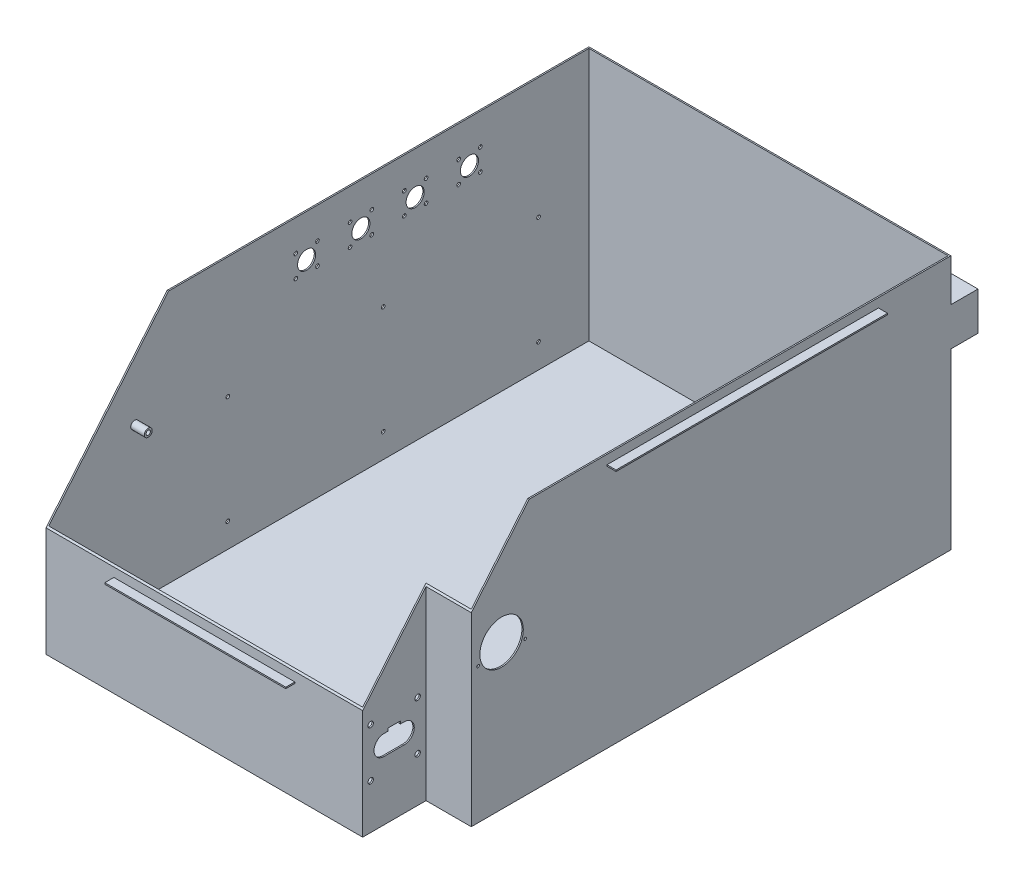
SolidWorks part; units mm, degrees
ref_plane "Front Plane" through (0, 0, 0) normal (0, 0, 1) x (1, 0, 0)
ref_plane "Top Plane" through (0, 0, 0) normal (0, 1, 0) x (1, 0, 0)
ref_plane "Right Plane" through (0, 0, 0) normal (1, 0, 0) x (0, 0, -1)
sketch "Sketch1" plane through (0, 0, 0) normal (0, 1, 0) x (1, 0, 0)
  line L1 (-200, 237.8263) -> (200, 237.8263)
  line L2 (-200, 237.8263) -> (-200, -362.1737)
  line L3 (-200, -362.1737) -> (150, -362.1737)
  line L4 (200, 237.8263) -> (200, -292.1737)
  line L6 (200, -292.1737) -> (150, -292.1737)
  line L7 (150, -292.1737) -> (150, -362.1737)
  line L8 (0, -55) -> (0, 55) construction
  point P1 (0, 237.8263)
  dimension "D1" = 600
  dimension "D2" = 400
  dimension "D5" = 70
  dimension "D6" = 50
extrude "Boss-Extrude1" add sketch "Sketch1" along normal blind 1.5
sketch "Sketch2" plane through (0, 1.5, 0) normal (0, 1, 0) x (1, 0, 0)
  line L60 (-198.5, 236.3263) -> (-198.5, -360.6737)
  line L61 (-198.5, -360.6737) -> (148.5, -360.6737)
  line L62 (148.5, -360.6737) -> (148.5, -290.6737)
  line L63 (148.5, -290.6737) -> (198.5, -290.6737)
  line L64 (198.5, -290.6737) -> (198.5, 236.3263)
  line L65 (198.5, 236.3263) -> (-198.5, 236.3263)
  line L66 (-200, 237.8263) -> (-200, -362.1737)
  line L67 (-200, -362.1737) -> (150, -362.1737)
  line L68 (150, -362.1737) -> (150, -292.1737)
  line L69 (150, -292.1737) -> (200, -292.1737)
  line L70 (200, -292.1737) -> (200, 237.8263)
  line L71 (200, 237.8263) -> (-200, 237.8263)
  line L72 (-200, 237.8263) -> (-200, -362.1737)
  line L73 (-200, -362.1737) -> (150, -362.1737)
  line L74 (150, -362.1737) -> (150, -292.1737)
  line L75 (150, -292.1737) -> (200, -292.1737)
  line L76 (200, -292.1737) -> (200, 237.8263)
  line L77 (200, 237.8263) -> (-200, 237.8263)
  dimension "D1" = 0
  dimension "D2" = 1.5
extrude "Boss-Extrude2" add sketch "Sketch2" along normal blind 280
sketch "Sketch3" plane through (-200, 0, 0) normal (-1, 0, 0) x (0, 0, 1)
  line L3 (362.1737, 281.5) -> (362.1737, 0) construction
  line L4 (362.1737, 121.1176) -> (228.1952, 281.5)
  line L6 (-237.8263, 281.5) -> (362.1737, 281.5) construction
  line L9 (362.1737, 281.5) -> (362.1737, 121.1176)
  line L10 (228.1952, 281.5) -> (362.1737, 281.5)
sketch "Sketch4" plane through (0, 0, -237.8263) normal (0, 0, -1) x (-1, 0, 0)
  line L0 (-200, 281.5) -> (-200, 0) construction
  line L1 (-200, 234.6761) -> (200, 234.6761)
  line L2 (-200, 234.6761) -> (-200, 192.2905)
  line L3 (-200, 192.2905) -> (200, 192.2905)
  line L4 (200, 234.6761) -> (200, 192.2905)
  line L5 (200, 281.5) -> (200, 0) construction
extrude "Boss-Extrude3" add sketch "Sketch4" along normal blind 30
extrude "Cut-Extrude1" cut sketch "Sketch3" against normal through all both and the other way through all
sketch "Sketch5" plane through (-200, 0, 0) normal (-1, 0, 0) x (0, 0, 1)
  line L0 (-116.3263, 223.1259) -> (-116.3263, 247.1259) construction
  line L5 (-116.3263, 223.1259) -> (-92.3263, 223.1259) construction
  line L6 (-116.3263, 247.1259) -> (-92.3263, 247.1259) construction
  line L7 (-92.3263, 223.1259) -> (-92.3263, 247.1259) construction
  line L8 (-116.3263, 223.1259) -> (-92.3263, 247.1259) construction
  line L9 (-116.3263, 247.1259) -> (-92.3263, 223.1259) construction
  line L10 (-56.3263, 223.1259) -> (-56.3263, 247.1259) construction
  line L11 (-56.3263, 223.1259) -> (-32.3263, 223.1259) construction
  line L12 (-56.3263, 247.1259) -> (-32.3263, 247.1259) construction
  line L13 (-32.3263, 223.1259) -> (-32.3263, 247.1259) construction
  line L14 (-56.3263, 223.1259) -> (-32.3263, 247.1259) construction
  line L15 (-56.3263, 247.1259) -> (-32.3263, 223.1259) construction
  line L16 (3.6737, 223.1259) -> (3.6737, 247.1259) construction
  line L17 (3.6737, 223.1259) -> (27.6737, 223.1259) construction
  line L18 (3.6737, 247.1259) -> (27.6737, 247.1259) construction
  line L19 (27.6737, 223.1259) -> (27.6737, 247.1259) construction
  line L20 (3.6737, 223.1259) -> (27.6737, 247.1259) construction
  line L21 (3.6737, 247.1259) -> (27.6737, 223.1259) construction
  line L22 (63.6737, 223.1259) -> (63.6737, 247.1259) construction
  line L23 (63.6737, 223.1259) -> (87.6737, 223.1259) construction
  line L24 (63.6737, 247.1259) -> (87.6737, 247.1259) construction
  line L25 (87.6737, 223.1259) -> (87.6737, 247.1259) construction
  line L26 (63.6737, 223.1259) -> (87.6737, 247.1259) construction
  line L27 (63.6737, 247.1259) -> (87.6737, 223.1259) construction
  line L28 (-236.3263, 281.5) -> (-236.3263, 1.5) construction
  circle A0 centre (-116.3263, 247.1259) radius 2
  circle A1 centre (-116.3263, 223.1259) radius 2
  circle A2 centre (-92.3263, 223.1259) radius 2
  circle A3 centre (-92.3263, 247.1259) radius 2
  circle A4 centre (-104.3263, 235.1259) radius 10
  circle A5 centre (-56.3263, 247.1259) radius 2
  circle A6 centre (-56.3263, 223.1259) radius 2
  circle A7 centre (-32.3263, 223.1259) radius 2
  circle A8 centre (-32.3263, 247.1259) radius 2
  circle A9 centre (-44.3263, 235.1259) radius 10
  circle A10 centre (3.6737, 247.1259) radius 2
  circle A11 centre (3.6737, 223.1259) radius 2
  circle A12 centre (27.6737, 223.1259) radius 2
  circle A13 centre (27.6737, 247.1259) radius 2
  circle A14 centre (15.6737, 235.1259) radius 10
  circle A15 centre (63.6737, 247.1259) radius 2
  circle A16 centre (63.6737, 223.1259) radius 2
  circle A17 centre (87.6737, 223.1259) radius 2
  circle A18 centre (87.6737, 247.1259) radius 2
  circle A19 centre (75.6737, 235.1259) radius 10
  point P9 (-104.3263, 235.1259)
  point P24 (-44.3263, 235.1259)
  point P38 (15.6737, 235.1259)
  point P52 (75.6737, 235.1259)
  dimension "D2" = 20
  dimension "D5" = 4
  dimension "D1" = 24
  dimension "D3" = 24
  dimension "D4" = 24
  dimension "D7" = 120
  dimension "D6" = 4
sketch "Sketch6" plane through (-198.5, 0, 0) normal (1, 0, 0) x (0, 0, -1)
  arc A0 (151.1392, 167.4539) -> (156.7272, 167.4539) centre (153.9332, 167.4539) ccw construction
  arc A1 (-68.8756, 167.4539) -> (-63.2876, 167.4539) centre (-66.0816, 167.4539) ccw construction
  arc A2 (-178.883, 167.4539) -> (-173.295, 167.4539) centre (-176.089, 167.4539) ccw construction
  arc A3 (151.1392, 167.4539) -> (156.7272, 167.4539) centre (153.9332, 167.4539) ccw
  arc A4 (-68.8756, 167.4539) -> (-63.2876, 167.4539) centre (-66.0816, 167.4539) ccw
  arc A5 (-178.883, 167.4539) -> (-173.295, 167.4539) centre (-176.089, 167.4539) ccw
  circle A6 centre (-176.089, 167.4539) radius 2.794
  circle A7 centre (-176.089, 167.4539) radius 4.5
  circle A8 centre (-64.4633, 167.4539) radius 4.5
  circle A9 centre (-64.4633, 167.4539) radius 2.794
  circle A10 centre (155.5515, 167.4539) radius 2.794
  circle A11 centre (155.5515, 167.4539) radius 4.5
  dimension "D1" = 9
extrude "Boss-Extrude4" [suppressed] add sketch "Sketch6" along normal blind 50 contours A4 A9 | A8 | A7 | A6 | A11 | A10
sketch "Sketch8" plane through (-198.5, 0, 0) normal (1, 0, 0) x (0, 0, -1)
  line L0 (236.3263, 1.5) -> (-360.6737, 1.5) construction
  line L1 (-360.6737, 122.9132) -> (-360.6737, 1.5) construction
  circle A0 centre (-265.6737, 172.2) radius 2.39
  circle A1 centre (-265.6737, 172.2) radius 4.39
  circle A2 centre (-265.6737, 16.5) radius 2.39
  circle A3 centre (-265.6737, 16.5) radius 4.39
  dimension "D3" = 4.78
  dimension "D4" = 2
  dimension "D1" = 155.7
  dimension "D2" = 15
  dimension "D5" = 95
extrude "Boss-Extrude5" add sketch "Sketch8" along normal blind 15
sketch "Sketch10" plane through (148.5, 0, 0) normal (-1, 0, 0) x (0, 0, 1)
  line L0 (316.1737, 86.5) -> (321.4237, 86.5) construction
  line L1 (316.1737, 66.5) -> (338.6737, 66.5) construction
  line L2 (338.6737, 76.5) -> (316.1737, 76.5) construction
  line L3 (360.6737, 1.5) -> (290.6737, 1.5) construction
  line L5 (321.4237, 86.5) -> (321.4237, 89.5) construction
  line L6 (321.4237, 89.5) -> (333.4237, 89.5) construction
  line L7 (333.4237, 86.5) -> (333.4237, 89.5) construction
  line L8 (360.6737, 122.9132) -> (360.6737, 1.5) construction
  line L9 (333.4237, 86.5) -> (338.6737, 86.5) construction
  line L10 (320.4237, 90.5) -> (334.4237, 90.5)
  line L11 (334.4237, 87.5) -> (334.4237, 90.5)
  line L12 (334.4237, 87.5) -> (338.6737, 87.5)
  line L13 (316.1737, 65.5) -> (338.6737, 65.5)
  line L14 (316.1737, 87.5) -> (320.4237, 87.5)
  line L15 (320.4237, 87.5) -> (320.4237, 90.5)
  line L17 (301.4737, 49.55) -> (353.3737, 49.55) construction
  line L18 (301.4737, 49.55) -> (301.4737, 103.45) construction
  line L19 (301.4737, 103.45) -> (353.3737, 103.45) construction
  line L20 (353.3737, 49.55) -> (353.3737, 103.45) construction
  line L21 (301.4737, 49.55) -> (353.3737, 103.45) construction
  line L22 (301.4737, 103.45) -> (353.3737, 49.55) construction
  arc A0 (316.1737, 86.5) -> (316.1737, 66.5) centre (316.1737, 76.5) ccw construction
  arc A1 (338.6737, 66.5) -> (338.6737, 86.5) centre (338.6737, 76.5) ccw construction
  arc A2 (338.6737, 65.5) -> (338.6737, 87.5) centre (338.6737, 76.5) ccw
  arc A3 (316.1737, 87.5) -> (316.1737, 65.5) centre (316.1737, 76.5) ccw
  circle A4 centre (301.4737, 103.45) radius 3
  circle A5 centre (353.3737, 103.45) radius 3
  circle A6 centre (301.4737, 49.55) radius 3
  circle A7 centre (353.3737, 49.55) radius 3
  point P12 (327.4237, 89.5)
  point P13 (327.4237, 76.5)
  point P26 (327.4237, 76.5)
  dimension "D1" = 65
  dimension "D2" = 22.5
  dimension "D6" = 20
  dimension "D10" = 6
  dimension "D3" = 22
  dimension "D4" = 12
  dimension "D5" = 3
  dimension "D8" = 51.9
  dimension "D9" = 53.9
  dimension "D7" = 1
extrude "Cut-Extrude2" cut sketch "Sketch10" against normal up to surface (1.5 mm away) contours L0 L7 L6 L5 | L2 A1 L0 A0 | A1 L2 A0 L1 | A0 | A1 | L14 A3 L13 A2 L12 L11 L10 L15 | A4 | A5 | A7 | A6 region at (148.5, 77.0724, 327.4237) region at (148.5, 103.45, 301.4737) region at (148.5, 103.45, 353.3737) region at (148.5, 49.55, 353.3737) up to face at (150, 81.5076, 327.1737)
sketch "Sketch11" plane through (148.5, 0, 0) normal (-1, 0, 0) x (0, 0, 1)
  line L0 (298.4737, 103.43) -> (298.4737, 49.53) construction
  line L13 (316.1737, 66.5) -> (338.6737, 66.5) construction
  line L14 (316.1737, 86.5) -> (321.4237, 86.5) construction
  line L15 (316.1737, 66.5) -> (338.6737, 66.5)
  line L19 (316.1737, 86.5) -> (318.4237, 86.5)
  line L20 (334.4237, 90.5) -> (320.4237, 90.5)
  line L21 (334.4237, 90.5) -> (320.4237, 90.5)
  line L22 (334.4237, 87.5) -> (334.4237, 90.5)
  line L23 (334.4237, 87.5) -> (334.4237, 90.5)
  line L28 (330.4237, 86.5) -> (321.4237, 86.5)
  line L29 (316.2509, 66) -> (338.7144, 66)
  line L30 (330.9237, 86) -> (320.7529, 86)
  line L31 (330.9237, 86) -> (330.9237, 91)
  line L32 (330.9237, 91) -> (317.9237, 91)
  line L33 (317.9237, 91) -> (317.9237, 87)
  line L34 (316.2509, 87) -> (317.9237, 87)
  line L36 (298.4737, 103.43) -> (350.3737, 103.43) construction
  line L43 (334.4237, 90.5) -> (320.4237, 90.5)
  line L44 (334.4237, 90.5) -> (320.4237, 90.5)
  line L45 (334.4237, 87.5) -> (334.4237, 90.5)
  line L46 (334.4237, 87.5) -> (334.4237, 90.5)
  line L47 (338.6737, 87.5) -> (334.4237, 87.5)
  line L48 (338.6737, 87.5) -> (334.4237, 87.5)
  line L49 (316.1737, 65.5) -> (338.6737, 65.5)
  line L50 (316.1737, 65.5) -> (338.6737, 65.5)
  line L51 (320.4237, 87.5) -> (316.1737, 87.5)
  line L52 (320.4237, 87.5) -> (316.1737, 87.5)
  line L53 (320.4237, 90.5) -> (320.4237, 87.5)
  line L54 (320.4237, 90.5) -> (320.4237, 87.5)
  line L55 (334.4237, 90.5) -> (320.4237, 90.5)
  line L56 (334.4237, 90.5) -> (320.4237, 90.5)
  line L57 (334.4237, 87.5) -> (334.4237, 90.5)
  line L58 (334.4237, 87.5) -> (334.4237, 90.5)
  line L59 (338.6737, 87.5) -> (334.4237, 87.5)
  line L60 (338.6737, 87.5) -> (334.4237, 87.5)
  line L61 (316.1737, 65.5) -> (338.6737, 65.5)
  line L62 (316.1737, 65.5) -> (338.6737, 65.5)
  line L63 (320.4237, 87.5) -> (316.1737, 87.5)
  line L64 (320.4237, 87.5) -> (316.1737, 87.5)
  line L65 (320.4237, 90.5) -> (320.4237, 87.5)
  line L66 (320.4237, 90.5) -> (320.4237, 87.5)
  line L67 (330.4237, 86.5) -> (330.4237, 90.5) construction
  line L68 (330.4237, 90.5) -> (318.4237, 90.5) construction
  line L69 (318.4237, 90.5) -> (318.4237, 86.5) construction
  line L70 (338.6737, 87.5) -> (334.4237, 87.5)
  line L71 (338.6737, 87.5) -> (334.4237, 87.5)
  line L72 (316.1737, 65.5) -> (338.6737, 65.5)
  line L73 (316.1737, 65.5) -> (338.6737, 65.5)
  line L74 (320.4237, 87.5) -> (316.1737, 87.5)
  line L75 (320.4237, 87.5) -> (316.1737, 87.5)
  line L76 (320.4237, 90.5) -> (320.4237, 87.5)
  line L77 (320.4237, 90.5) -> (320.4237, 87.5)
  arc A4 (338.7144, 66) -> (320.7529, 86) centre (336.1498, 81.7622) ccw
  arc A5 (338.6737, 65.5) -> (338.6737, 87.5) centre (338.6737, 76.5) ccw
  arc A7 (338.6737, 65.5) -> (338.6737, 87.5) centre (338.6737, 76.5) ccw
  arc A9 (316.2509, 87) -> (316.2509, 66) centre (312.9721, 76.5) ccw
  circle A10 centre (298.4737, 103.43) radius 3
  circle A11 centre (298.4737, 49.53) radius 3
  circle A12 centre (350.3737, 103.43) radius 3
  circle A13 centre (350.3737, 49.53) radius 3
  arc A16 (338.6737, 66.5) -> (321.4237, 86.5) centre (336.1498, 81.7622) ccw construction
  arc A17 (338.6737, 65.5) -> (338.6737, 87.5) centre (338.6737, 76.5) ccw
  arc A18 (316.1737, 87.5) -> (316.1737, 65.5) centre (316.1737, 76.5) ccw
  arc A19 (316.1737, 87.5) -> (316.1737, 65.5) centre (316.1737, 76.5) ccw
  arc A20 (316.1737, 86.5) -> (316.1737, 66.5) centre (312.9721, 76.5) ccw construction
  arc A21 (338.6737, 65.5) -> (338.6737, 87.5) centre (338.6737, 76.5) ccw
  arc A22 (316.1737, 87.5) -> (316.1737, 65.5) centre (316.1737, 76.5) ccw
  arc A23 (316.1737, 87.5) -> (316.1737, 65.5) centre (316.1737, 76.5) ccw
  arc A24 (338.6737, 65.5) -> (338.6737, 87.5) centre (338.6737, 76.5) ccw
  arc A25 (338.6737, 65.5) -> (338.6737, 87.5) centre (338.6737, 76.5) ccw
  arc A26 (316.1737, 87.5) -> (316.1737, 65.5) centre (316.1737, 76.5) ccw
  arc A27 (316.1737, 87.5) -> (316.1737, 65.5) centre (316.1737, 76.5) ccw
  dimension "D5" = 6
  dimension "D6" = 51.9
  dimension "D7" = 53.9
  dimension "D1" = 0
  dimension "D2" = 0
  dimension "D3" = 0
  dimension "D4" = 0.5
extrude "Cut-Extrude3" [suppressed] cut sketch "Sketch11" against normal through all
sketch "Sketch14" plane through (148.5, 0, 0) normal (-1, 0, 0) x (0, 0, 1)
  line L0 (362.1737, 121.1176) -> (362.1737, 0) construction
  line L1 (362.1737, 0) -> (292.1737, 0) construction
  circle A0 centre (297.2737, 103.43) radius 3
  circle A1 centre (349.1737, 103.43) radius 3
  circle A2 centre (349.1737, 49.53) radius 3
  circle A3 centre (297.2737, 49.53) radius 3
  dimension "D5" = 6
  dimension "D1" = 51.9
  dimension "D2" = 53.9
  dimension "D3" = 13
  dimension "D4" = 103.43
extrude "Cut-Extrude4" [suppressed] cut sketch "Sketch14" against normal up to surface (1.5 mm away) up to face at (150, 49.55, 304.4737)
sketch "Sketch15" plane through (198.5, 0, 0) normal (-1, 0, 0) x (0, 0, 1)
  line L1 (-151.3263, 252.1363) -> (-136.3263, 252.1363)
  line L2 (-151.3263, 252.1363) -> (-151.3263, 250.6363)
  line L3 (-151.3263, 250.6363) -> (-136.3263, 250.6363)
  line L4 (-136.3263, 252.1363) -> (-136.3263, 250.6363)
  line L5 (-236.3263, 281.5) -> (-236.3263, 1.5) construction
  line L6 (126.6737, 252.1363) -> (146.6737, 252.1363)
  line L7 (126.6737, 250.6363) -> (146.6737, 250.6363)
  line L8 (126.6737, 252.1363) -> (126.6737, 250.6363)
  line L9 (146.6737, 252.1363) -> (146.6737, 250.6363)
  dimension "D1" = 1.5
  dimension "D2" = 15
  dimension "D3" = 85
  dimension "D4" = 363
  dimension "D5" = 20
extrude "Boss-Extrude6" add sketch "Sketch15" along normal blind 13
ref_plane "Plane1" through (0, 0, -131.3263) normal (0, 0, -1) x (-1, 0, 0)
sketch "Sketch17" plane through (0, 0, -136.3263) normal (0, 0, 1) x (1, 0, 0)
  line L0 (198.5, 250.6363) -> (198.5, 235.6363)
  line L1 (198.5, 281.5) -> (198.5, 206.7085) construction
  line L2 (198.5, 235.6363) -> (185.5, 250.6363)
  line L3 (185.5, 250.6363) -> (198.5, 250.6363)
  dimension "D1" = 15
extrude "Boss-Extrude7" add sketch "Sketch17" against normal blind 1.5
ref_plane "Plane2" through (0, 0, 126.6737) normal (0, 0, 1) x (1, 0, 0)
sketch "Sketch18" plane through (0, 0, 126.6737) normal (0, 0, 1) x (1, 0, 0)
  line L0 (198.5, 250.6363) -> (198.5, 235.6363)
  line L1 (198.5, 281.5) -> (198.5, 206.7085) construction
  line L2 (198.5, 235.6363) -> (185.5, 250.6363)
  line L3 (185.5, 250.6363) -> (198.5, 250.6363)
  dimension "D1" = 15
extrude "Boss-Extrude8" add sketch "Sketch18" along normal blind 1.5
sketch "Sketch20" plane through (0, 252.1363, 0) normal (0, 1, 0) x (1, 0, 0)
  line L1 (185.5, 151.3263) -> (198.5, 151.3263) construction
  line L2 (185.5, 136.3263) -> (185.5, 151.3263) construction
  line L3 (185.5, -146.6737) -> (198.5, -146.6737) construction
  line L4 (185.5, -146.6737) -> (185.5, -126.6737) construction
  circle A0 centre (193, 144.3263) radius 2.4159
  circle A1 centre (195.5, -139.6737) radius 2
  dimension "D3" = 4
  dimension "D1" = 7
  dimension "D2" = 7.5
  dimension "D4" = 7
  dimension "D5" = 10
extrude "Cut-Extrude5" cut sketch "Sketch20" against normal up to surface (1.5 mm away) up to face at (192, 250.6363, -144.5763)
extrude "Cut-Extrude7" cut sketch "Sketch5" against normal up to surface (1.5 mm away) up to face at (-198.5, 16.5, 261.2837)
sketch "Sketch21" plane through (0, 0, -237.8263) normal (0, 0, -1) x (-1, 0, 0)
  line L0 (-200, 281.5) -> (200, 281.5) construction
  line L1 (-150, 271.5) -> (150, 271.5)
  line L2 (-150, 271.5) -> (-150, 270)
  line L3 (-150, 270) -> (150, 270)
  line L4 (150, 271.5) -> (150, 270)
  point P6 (0, 281.5)
  point P7 (0, 271.5)
  dimension "D1" = 1.5
  dimension "D2" = 300
  dimension "D3" = 10
extrude "Boss-Extrude9" add sketch "Sketch21" along normal blind 10
sketch "Sketch22" plane through (-200, 0, 0) normal (-1, 0, 0) x (0, 0, 1)
  line L0 (-237.8263, 281.5) -> (228.1952, 281.5) construction
  line L1 (-157.8263, 271.5) -> (142.1737, 271.5)
  line L2 (-157.8263, 271.5) -> (-157.8263, 270)
  line L3 (-157.8263, 270) -> (142.1737, 270)
  line L4 (142.1737, 271.5) -> (142.1737, 270)
  line L5 (-237.8263, 281.5) -> (-237.8263, 234.6761) construction
  dimension "D1" = 1.5
  dimension "D2" = 10
  dimension "D3" = 80
  dimension "D4" = 300
extrude "Boss-Extrude10" add sketch "Sketch22" along normal blind 10
ref_plane "Plane3" through (0, 0, -77.8263) normal (0, 0, -1) x (-1, 0, 0)
sketch "Sketch23" plane through (0, 0, -77.8263) normal (0, 0, -1) x (-1, 0, 0)
  line L0 (210, 270) -> (200, 270) construction
  line L1 (210, 270) -> (200, 270)
  line L2 (210, 270) -> (200, 260)
  line L3 (200, 281.5) -> (200, 234.6761) construction
  line L4 (200, 260) -> (200, 270)
  dimension "D1" = 10
extrude "Boss-Extrude11" add sketch "Sketch23" along normal mid plane 1.5
ref_plane "Plane4" through (0, 0, 52.1737) normal (0, 0, 1) x (1, 0, 0)
sketch "Sketch24" plane through (0, 0, 52.1737) normal (0, 0, 1) x (1, 0, 0)
  line L6 (-210, 270) -> (-200, 260)
  line L7 (-200, 260) -> (-200, 270)
  line L8 (-200, 270) -> (-210, 270)
  line L9 (-210, 270) -> (-200, 260)
  line L10 (-200, 260) -> (-200, 270)
  line L11 (-200, 270) -> (-210, 270)
  dimension "D1" = 0
extrude "Boss-Extrude12" add sketch "Sketch24" along normal mid plane 1.5
ref_plane "Plane5" through (100, 0, 0) normal (1, 0, 0) x (0, 0, -1)
sketch "Sketch25" plane through (100, 0, 0) normal (1, 0, 0) x (0, 0, -1)
  line L0 (247.8263, 270) -> (237.8263, 270)
  line L1 (237.8263, 270) -> (237.8263, 260)
  line L2 (237.8263, 281.5) -> (237.8263, 234.6761) construction
  line L3 (237.8263, 260) -> (247.8263, 270)
  dimension "D1" = 10
extrude "Boss-Extrude13" add sketch "Sketch25" along normal mid plane 1.5
ref_plane "Plane6" through (-100, 0, 0) normal (-1, 0, 0) x (0, 0, 1)
sketch "Sketch26" plane through (-100, 0, 0) normal (-1, 0, 0) x (0, 0, 1)
  line L3 (-247.8263, 270) -> (-237.8263, 260)
  line L4 (-237.8263, 260) -> (-237.8263, 270)
  line L5 (-237.8263, 270) -> (-247.8263, 270)
  line L6 (-247.8263, 270) -> (-237.8263, 260)
  line L7 (-237.8263, 260) -> (-237.8263, 270)
  line L8 (-237.8263, 270) -> (-247.8263, 270)
  dimension "D1" = 0
extrude "Boss-Extrude14" add sketch "Sketch26" along normal mid plane 1.5
mirror "Mirror1" about plane through (0, 0, 0) normal (1, 0, 0) of "Boss-Extrude11", "Boss-Extrude12", "Boss-Extrude10"
sketch "Sketch27" plane through (0, 0, 362.1737) normal (0, 0, 1) x (1, 0, 0)
  line L0 (150, 121.1176) -> (-200, 121.1176) construction
  line L1 (-125, 111.1176) -> (75, 111.1176)
  line L2 (-125, 111.1176) -> (-125, 109.6176)
  line L3 (-125, 109.6176) -> (75, 109.6176)
  line L4 (75, 111.1176) -> (75, 109.6176)
  line L5 (150, 121.1176) -> (-200, 121.1176) construction
  point P6 (-25, 121.1176)
  point P7 (-25, 111.1176)
  dimension "D1" = 1.5
  dimension "D2" = 200
  dimension "D3" = 10
extrude "Boss-Extrude15" add sketch "Sketch27" along normal blind 10
ref_plane "Plane7" through (-95, 0, 0) normal (-1, 0, 0) x (0, 0, 1)
sketch "Sketch28" plane through (-95, 0, 0) normal (-1, 0, 0) x (0, 0, 1)
  line L0 (372.1737, 109.6176) -> (362.1737, 109.6176)
  line L1 (362.1737, 109.6176) -> (362.1737, 99.6176)
  line L2 (362.1737, 121.1176) -> (362.1737, 0) construction
  line L3 (362.1737, 99.6176) -> (372.1737, 109.6176)
  dimension "D1" = 10
extrude "Boss-Extrude16" add sketch "Sketch28" along normal mid plane 1.5
ref_plane "Plane8" through (45, 0, 0) normal (1, 0, 0) x (0, 0, -1)
sketch "Sketch29" plane through (45, 0, 0) normal (1, 0, 0) x (0, 0, -1)
  line L3 (-372.1737, 109.6176) -> (-362.1737, 99.6176)
  line L4 (-362.1737, 99.6176) -> (-362.1737, 109.6176)
  line L5 (-362.1737, 109.6176) -> (-372.1737, 109.6176)
  line L6 (-372.1737, 109.6176) -> (-362.1737, 99.6176)
  line L7 (-362.1737, 99.6176) -> (-362.1737, 109.6176)
  line L8 (-362.1737, 109.6176) -> (-372.1737, 109.6176)
  dimension "D1" = 0
extrude "Boss-Extrude17" add sketch "Sketch29" along normal mid plane 1.5
sketch "Sketch30" plane through (200, 0, 0) normal (1, 0, 0) x (0, 0, -1)
  line L1 (-292.1737, 0) -> (237.8263, 0) construction
  line L2 (-292.1737, 204.9129) -> (-292.1737, 0) construction
  circle A0 centre (-258.6737, 160) radius 24
  circle A1 centre (-284.6737, 150) radius 1.5
  circle A2 centre (-232.6737, 150) radius 1.5
  dimension "D1" = 48
  dimension "D2" = 3
  dimension "D3" = 3
  dimension "D4" = 26
  dimension "D5" = 10
  dimension "D6" = 26
  dimension "D7" = 10
  dimension "D8" = 160
  dimension "D9" = 33.5
extrude "Cut-Extrude8" cut sketch "Sketch30" against normal up to surface (1.5 mm away) up to face at (198.5, 246.1363, -141.8263)
sketch "Sketch31" plane through (0, 0, 0) normal (0, -1, 0) x (1, 0, 0)
  line L0 (200, -237.8263) -> (-200, -237.8263) construction
  line L1 (200, -213.8263) -> (220, -213.8263)
  line L2 (200, -213.8263) -> (200, -237.8263)
  line L3 (200, -237.8263) -> (225, -237.8263)
  line L4 (220, -213.8263) -> (225, -237.8263)
  line L64 (200, 228.1952) -> (200, -237.8263) construction
  line L65 (200, -88.0763) -> (220, -88.0763)
  line L66 (200, -88.0763) -> (200, -112.0763)
  line L67 (200, -112.0763) -> (225, -112.0763)
  line L68 (220, -88.0763) -> (225, -112.0763)
  line L69 (200, 37.6737) -> (220, 37.6737)
  line L70 (200, 37.6737) -> (200, 13.6737)
  line L71 (200, 13.6737) -> (225, 13.6737)
  line L72 (220, 37.6737) -> (225, 13.6737)
  line L73 (200, 163.4237) -> (220, 163.4237)
  line L74 (200, 163.4237) -> (200, 139.4237)
  line L75 (200, 139.4237) -> (225, 139.4237)
  line L76 (220, 163.4237) -> (225, 139.4237)
  line L77 (200, 289.1737) -> (220, 289.1737)
  line L78 (200, 289.1737) -> (200, 265.1737)
  line L79 (200, 265.1737) -> (225, 265.1737)
  line L80 (220, 289.1737) -> (225, 265.1737)
  circle A0 centre (222.5, -225.8263) radius 12.2577
  circle A1 centre (222.5, -225.8263) radius 4
  circle A30 centre (222.5, -100.0763) radius 12.2577
  circle A31 centre (222.5, -100.0763) radius 4
  circle A32 centre (222.5, 25.6737) radius 12.2577
  circle A33 centre (222.5, 25.6737) radius 4
  circle A34 centre (222.5, 151.4237) radius 12.2577
  circle A35 centre (222.5, 151.4237) radius 4
  circle A36 centre (222.5, 277.1737) radius 12.2577
  circle A37 centre (222.5, 277.1737) radius 4
  dimension "D3" = 8
  dimension "D1" = 24
  dimension "D2" = 20
  dimension "D5" = 101.75
  dimension "D4" = 5
extrude "Boss-Extrude18" [suppressed] add sketch "Sketch31" against normal blind 1.5 separate body
sketch "Sketch33" plane through (-200, 0, 0) normal (-1, 0, 0) x (0, 0, 1)
  line L0 (-237.8263, 192.2905) -> (-237.8263, 0) construction
  line L1 (-237.8263, 0) -> (362.1737, 0) construction
  circle A0 centre (-180.6263, 147.77) radius 2
  circle A1 centre (-180.6263, 28.39) radius 2
  circle A2 centre (-8.9263, 147.77) radius 2
  circle A3 centre (-8.9263, 28.39) radius 2
  circle A4 centre (162.7737, 147.77) radius 2
  circle A5 centre (162.7737, 28.39) radius 2
  dimension "D3" = 4
  dimension "D1" = 57.2
  dimension "D2" = 119.38
  dimension "D4" = 28.39
  dimension "D5" = 3
extrude "Cut-Extrude9" cut sketch "Sketch33" against normal up to surface (1.5 mm away) up to face at (-198.5, 223.1259, 25.6737)
mirror "Mirror2" [suppressed] about plane through (0, 0, 0) normal (1, 0, 0)
